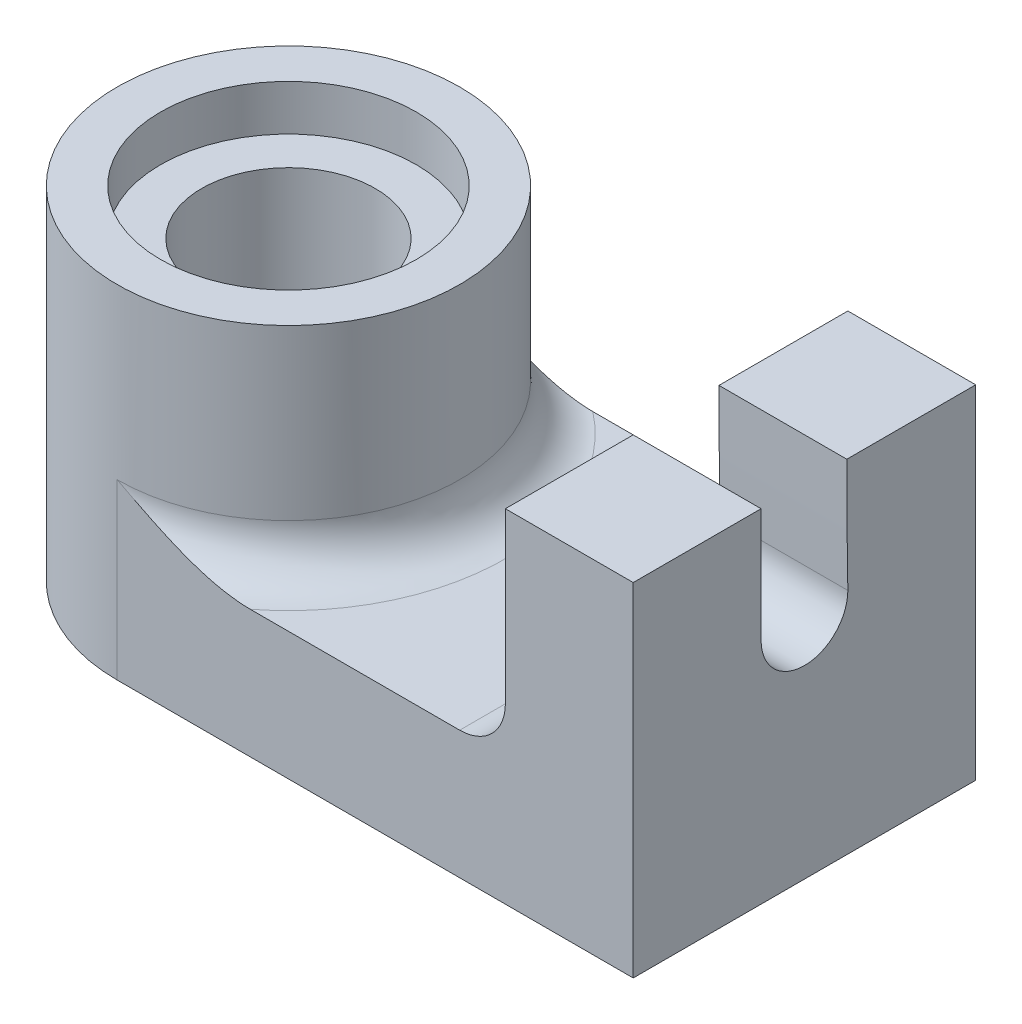
SolidWorks part; units mm, degrees
ref_plane "Front Plane" through (0, 0, 0) normal (0, 0, 1) x (1, 0, 0)
ref_plane "Top Plane" through (0, 0, 0) normal (0, 1, 0) x (1, 0, 0)
ref_plane "Right Plane" through (0, 0, 0) normal (1, 0, 0) x (0, 0, -1)
sketch "Sketch1" plane through (0, 0, 0) normal (0, 0, 1) x (1, 0, 0)
  line L0 (0, 0) -> (113, 0)
  line L1 (113, 0) -> (113, 75)
  line L2 (113, 75) -> (85, 75)
  line L3 (85, 75) -> (85, 28)
  line L4 (0, 28) -> (85, 28)
  line L5 (0, 28) -> (0, 0)
  dimension "D1" = 113
  dimension "D2" = 75
  dimension "D3" = 28
  dimension "D4" = 28
extrude "Boss-Extrude1" add sketch "Sketch1" along normal mid plane 75
sketch "Sketch3" plane through (113, 0, 0) normal (1, 0, 0) x (0, 0, -1)
  line L0 (0, 75) -> (-9.5, 75)
  line L1 (-37.5, 75) -> (37.5, 75) construction
  line L2 (-9.5, 75) -> (-9.5, 50)
  line L3 (0, 75) -> (9.2756, 75)
  line L4 (37.5, 0) -> (37.5, 75) construction
  arc A0 (-9.5, 50) -> (9.494, 50.3387) centre (0, 50) ccw
  arc A1 (9.2756, 75) -> (9.5, 50) centre (1401.9106, 75) ccw
  line M4 (37.5, 75) -> (-37.5, 75)
  dimension "D3" = 19
  dimension "D4" = 1392.6351
  dimension "D1" = 9.5
  dimension "D2" = 25
  dimension "D5" = 1364.4106
extrude "Cut-Extrude1" cut sketch "Sketch3" against normal blind 75 contours A1 L2 A0 M4 region at (113, 58.6579, 0.0574)
sketch "Sketch5" plane through (0, 0, 0) normal (0, -1, 0) x (1, 0, 0)
  line L0 (0, 37.5) -> (0, -37.5) construction
  circle A0 centre (0, 0) radius 37.5
  circle A1 centre (0, 0) radius 19
  dimension "D1" = 75
  dimension "D2" = 38
extrude "Boss-Extrude2" add sketch "Sketch5" against normal blind 75
sketch "Sketch6" plane through (0, 75, 0) normal (0, 1, 0) x (1, 0, 0)
  circle A0 centre (0, 0) radius 19 construction
  circle A1 centre (0, 0) radius 19
extrude "Cut-Extrude2" cut sketch "Sketch6" against normal blind 75
sketch "Sketch7" plane through (0, 75, 0) normal (0, 1, 0) x (1, 0, 0)
  circle A0 centre (0, 0) radius 28
  dimension "D1" = 56
extrude "Cut-Extrude3" cut sketch "Sketch7" against normal blind 10
ref_plane "Plane1" through (0, 37.5, 0) normal (0, 1, 0) x (1, 0, 0)
mirror "Mirror1" about plane through (0, 37.5, 0) normal (0, 1, 0) of "Cut-Extrude3"
fillet "Fillet1" radius 10 2 edges at (85, 28, 0) (37.5, 28, 0)
sketch "Sketch8" plane through (0, 65, 0) normal (0, 1, 0) x (1, 0, 0)
  line L1 (18.3303, 5) -> (22, 5)
  line L3 (18.3303, -5) -> (22, -5)
  line L4 (22, 5) -> (22, -5)
  circle A0 centre (0, 0) radius 19 construction
  arc A1 (18.3303, -5) -> (18.3303, 5) centre (0, 0) ccw
  point P0 (19, 0)
  point P7 (0, 0)
  point P9 (-19, 0)
  dimension "D2" = 41
  dimension "D1" = 10
extrude "Cut-Extrude4" cut sketch "Sketch8" against normal blind 100
